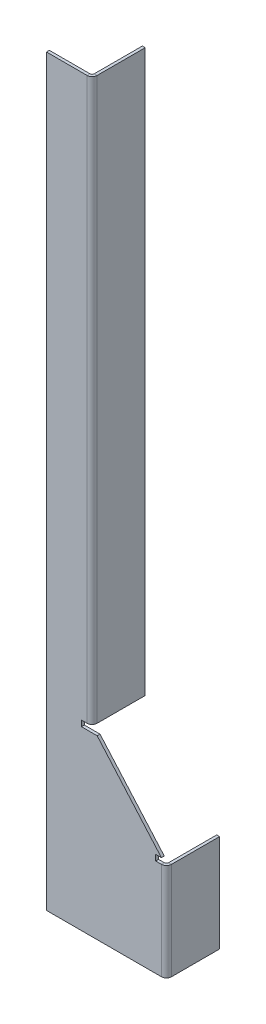
SolidWorks part; units mm, degrees
note: The reader was unsure of these and kept them because the rebuilt part matched: flange length of "Edge-Flange1".
ref_plane "Front Plane" through (0, 0, 0) normal (0, 0, 1) x (1, 0, 0)
ref_plane "Top Plane" through (0, 0, 0) normal (0, 1, 0) x (1, 0, 0)
ref_plane "Right Plane" through (0, 0, 0) normal (1, 0, 0) x (0, 0, -1)
sketch "Sketch1" plane through (0, 0, 0) normal (0, 0, 1) x (1, 0, 0)
  line L0 (43, 700) -> (0, 700)
  line L1 (0, 700) -> (0, 0)
  line L2 (0, 0) -> (113, 0)
  line L3 (113, 0) -> (113, 91.7)
  line L4 (113, 91.7) -> (43, 171.7)
  line L5 (43, 171.7) -> (43, 700)
  dimension "D1" = 700
  dimension "D2" = 43
  dimension "D3" = 91.7
  dimension "D4" = 80
  dimension "D5" = 70
base flange "Base-Flange1" sketch "Sketch1" thickness 2.7 reverse thickness direction no parameters "D1"=2
edge flange "Edge-Flange1" sketch "Sketch10" flange profiles "Sketch10", "Sketch11" flange angle 90 flange length 50 flange position material inside bend radius 2 thickness 2.7 relief rectangular parameters "D6"=10, "D8"=1
sketch "Sketch10" plane through (113, 0, -2.7) normal (-1, 0, 0) x (0, 1, 0)
  line L2 (0, 0) -> (0, 47.3)
  line L3 (0, 47.3) -> (91.7, 47.3)
  line L4 (91.7, 47.3) -> (91.7, 0)
  line L5 (91.7, 0) -> (0, 0) construction
  line L6 (91.7, 0) -> (0, 0)
sketch "Sketch11" plane through (43, 0, -2.7) normal (-1, 0, 0) x (0, 1, 0)
  line L0 (700, 0) -> (171.7, 0) construction
  line L1 (700, 0) -> (171.7, 0)
  line L2 (700, 0) -> (700, 47.3)
  line L3 (700, 47.3) -> (171.7, 47.3)
  line L4 (171.7, 47.3) -> (171.7, 0)
bend "EdgeBend1" bend radius 2 bend angle 90 parameters "D5"=1
bend "EdgeBend2" bend radius 2 bend angle 90 parameters "D5"=2
sketch "Bend-Lines1" [suppressed] plane through (0, 0, 0) normal (0, 1, 0) x (1, 0, 0)
sketch "Bounding-Box1" [suppressed] plane through (0, 0, 0) normal (0, 1, 0) x (1, 0, 0)
sheet metal parameters "Sheet-Metal1" thickness 2.7 parameters "D1"=2
flat pattern "Flat-Pattern1" [suppressed]
sketch "Bend-Lines2" plane through (0, 0, 0) normal (0, 1, 0) x (1, 0, 0)
sketch3d "Bounding-Box2" [suppressed]
  line L0 (-113, 700, 0) -> (-113, 0, 0) construction
  line L1 (0, 700, 0) -> (0, 0, 0) construction
  line L2 (-113, 700, 0) -> (0, 700, 0) construction
  line L3 (-113, 0, 0) -> (0, 0, 0) construction
sheet metal parameters "Sheet-Metal2" thickness 2.7 parameters "D1"=2
flat pattern "Flat-Pattern1"
sketch "Bend-Lines2" plane through (0, 0, 0) normal (0, 0, 1) x (1, 0, 0)
  line L0 (40.9311, 171.7) -> (40.9311, 700) construction
  line L1 (110.9311, 0) -> (110.9311, 91.7) construction
  line L2 (40.9311, 171.7) -> (40.9311, 700) construction
  line L3 (110.9311, 0) -> (110.9311, 91.7) construction
sketch3d "Bounding-Box2" [suppressed]
  line L0 (158.8622, 700, 0) -> (158.8622, 0, 0) construction
  line L1 (0, 700, 0) -> (0, 0, 0) construction
  line L2 (158.8622, 700, 0) -> (0, 700, 0) construction
  line L3 (158.8622, 0, 0) -> (0, 0, 0) construction
bend of the flat pattern "Flatten-<EdgeBend1>1"
bend of the flat pattern "Flatten-<EdgeBend2>1"
